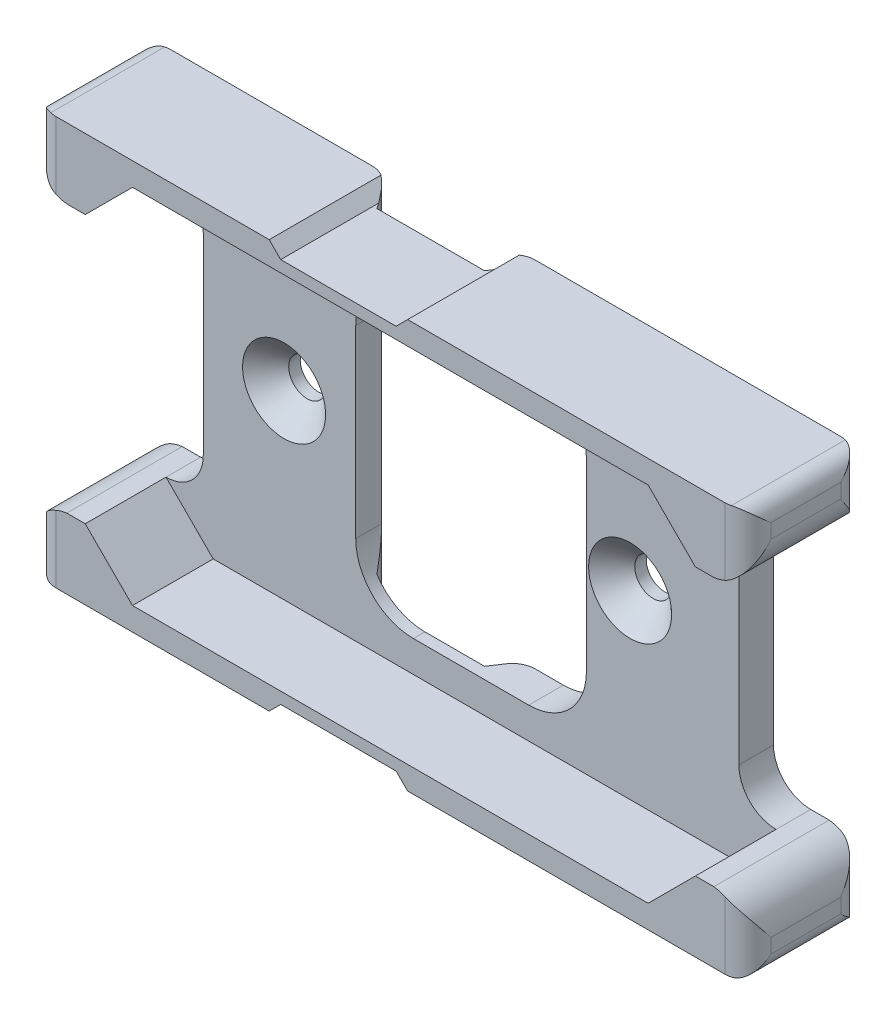
SolidWorks part; units mm, degrees
material "PET"
ref_plane "Front Plane" through (0, 0, 0) normal (0, 0, 1) x (1, 0, 0)
ref_plane "Top Plane" through (0, 0, 0) normal (0, 1, 0) x (1, 0, 0)
ref_plane "Right Plane" through (0, 0, 0) normal (1, 0, 0) x (0, 0, -1)
sketch "Sketch1" plane through (0, 0, 0) normal (0, 0, 1) x (1, 0, 0)
  line L0 (-31, 0) -> (31, 0)
  line L1 (31, 0) -> (31, 2.75)
  line L2 (28.0482, 6.094) -> (26.4482, 6.094)
  line L3 (26.4482, 6.094) -> (22.3542, 2)
  line L4 (22.3542, 2) -> (-22.3542, 2)
  line L5 (0, -3.5946) -> (0, 25.5961) construction
  line L6 (31, 17.7) -> (-31.0965, 17.7) construction
  line L7 (-26.4482, 6.094) -> (-22.3542, 2)
  line L8 (-31, 0) -> (-31, 2.75)
  line L9 (-28.0482, 6.094) -> (-26.4482, 6.094)
  line L10 (-28.0482, 29.306) -> (-26.4482, 29.306)
  line L11 (-31, 35.4) -> (-31, 32.65)
  line L12 (-26.4482, 29.306) -> (-22.3542, 33.4)
  line L13 (22.3542, 33.4) -> (-22.3542, 33.4)
  line L14 (26.4482, 29.306) -> (22.3542, 33.4)
  line L15 (28.0482, 29.306) -> (26.4482, 29.306)
  line L16 (31, 35.4) -> (31, 32.65)
  line L17 (-31, 35.4) -> (31, 35.4)
  arc A0 (31, 2.75) -> (28.0482, 6.094) centre (27.63, 2.75) ccw
  arc A1 (-31, 2.75) -> (-28.0482, 6.094) centre (-27.63, 2.75) cw
  arc A2 (-31, 32.65) -> (-28.0482, 29.306) centre (-27.63, 32.65) ccw
  arc A3 (31, 32.65) -> (28.0482, 29.306) centre (27.63, 32.65) cw
  point P18 (0, 2)
  point P19 (0, 0)
  point P25 (0, 35.4)
  point P26 (0, 33.4)
  dimension "D1" = 31
  dimension "D5" = 3.37
  dimension "D2" = 0.75
  dimension "D3" = 1.6
  dimension "D4" = 135
  dimension "D6" = 2
  dimension "D7" = 17.7
extrude "PCB Edge Guide" add sketch "Sketch1" along normal blind 7
sketch "Sketch2" plane through (0, 0, 0) normal (0, 0, -1) x (-1, 0, 0)
  line L1 (-31, 35.4) -> (31, 35.4)
  line L2 (-31, 35.4) -> (-31, 0)
  line L3 (-31, 0) -> (31, 0)
  line L4 (31, 35.4) -> (31, 0)
extrude "Rear Main Body" add sketch "Sketch2" along normal blind 3
fillet "Fillet1" radius 1.5 4 edges at (31, 0, 2) (31, 35.4, 2) (-31, 0, 2) (-31, 35.4, 2)
sketch "Sketch3" plane through (0, 2, 0) normal (0, 1, 0) x (1, 0, 0)
  line L0 (22.3542, -7) -> (-22.3542, -7) construction
  line L1 (-14, -7) -> (6, -7)
  line L2 (-14, -7) -> (-14, -4.7)
  line L3 (-14, -4.7) -> (6, -4.7)
  line L4 (6, -7) -> (6, -4.7)
  line L5 (0, 0) -> (0, -7) construction
  line L6 (22.3542, 0) -> (-22.3542, 0) construction
  dimension "D1" = 2.3
  dimension "D2" = 20
  dimension "D3" = 6
extrude "Lower PCB Fixture Tab" [suppressed] add sketch "Sketch3" along normal blind 2
sketch "Sketch4" plane through (0, 0, 7) normal (0, 0, 1) x (1, 0, 0)
  line L0 (0, 35.4) -> (0, 0) construction
  line L1 (29.5, 35.4) -> (-29.5, 35.4) construction
  line L2 (-31, 17.7) -> (31, 17.7) construction
  line L3 (-31, 2.75) -> (-31, 32.65) construction
  line L4 (31, 32.65) -> (31, 2.75) construction
  line L5 (-9, 0) -> (-9, 1)
  line L6 (0, 35.4) -> (-9, 35.4)
  line L7 (0, 35.4) -> (0, 34.4)
  line L8 (0, 34.4) -> (-9, 34.4)
  line L9 (-9, 35.4) -> (-9, 34.4)
  line L10 (0, 1) -> (-9, 1)
  line L11 (0, 0) -> (0, 1)
  line L12 (0, 0) -> (-9, 0)
  dimension "D1" = 1
  dimension "D2" = 9
extrude "Cable Tie Cutout" cut sketch "Sketch4" against normal through all
chamfer "Cable Tie Chamfer1" distance 1.5 angle 45 4 edges at (-9, 0, 2) (0, 0, 2) (-9, 35.4, 2) (0, 35.4, 2)
chamfer "Cable Tie Chamfer2" distance 1.5 angle 45 2 edges at (-4.5, 34.4, -3) (-4.5, 1, -3)
sketch "Sketch5" plane through (0, 0, -3) normal (0, 0, -1) x (-1, 0, 0)
  line L0 (-31, 17.7) -> (31, 17.7) construction
  line L1 (8, 30.7) -> (10, 30.7)
  line L2 (8, 30.7) -> (8, 4.7)
  line L3 (8, 4.7) -> (10, 4.7)
  line L4 (10, 30.7) -> (10, 4.7)
  line L5 (-31, 33.9) -> (-31, 1.5) construction
  line L6 (31, 1.5) -> (31, 33.9) construction
  line L7 (3.5, 30.7) -> (5.5, 30.7)
  line L8 (5.5, 30.7) -> (5.5, 4.7)
  line L9 (3.5, 30.7) -> (3.5, 4.7)
  line L10 (3.5, 4.7) -> (5.5, 4.7)
  line L11 (-1, 30.7) -> (1, 30.7)
  line L12 (1, 30.7) -> (1, 4.7)
  line L13 (-1, 30.7) -> (-1, 4.7)
  line L14 (-1, 4.7) -> (1, 4.7)
  line L15 (-5.5, 30.7) -> (-3.5, 30.7)
  line L16 (-3.5, 30.7) -> (-3.5, 4.7)
  line L17 (-5.5, 30.7) -> (-5.5, 4.7)
  line L18 (-5.5, 4.7) -> (-3.5, 4.7)
  line L19 (-10, 30.7) -> (-8, 30.7)
  line L20 (-8, 30.7) -> (-8, 4.7)
  line L21 (-10, 30.7) -> (-10, 4.7)
  line L22 (-10, 4.7) -> (-8, 4.7)
  dimension "D1" = 26
  dimension "D2" = 2
  dimension "D3" = 21
  dimension "D4" = 5
extrude "Rear Vents" cut sketch "Sketch5" against normal up to surface (3 mm away) up to face at (0, 17.7, 0)
sketch "Sketch6" plane through (0, 0, -3) normal (0, 0, -1) x (-1, 0, 0)
  line L0 (-31, 17.7) -> (31, 17.7) construction
  line L1 (-31, 33.9) -> (-31, 1.5) construction
  line L2 (31, 1.5) -> (31, 33.9) construction
  circle A0 centre (-13.79, 17.7) radius 1.6
  circle A1 centre (16.21, 17.7) radius 1.6
  dimension "D1" = 30
  dimension "D3" = 3.2
  dimension "D2" = 17.21
extrude "Cut-Extrude3" cut sketch "Sketch6" against normal up to next
chamfer "Chamfer3" distance 2 angle 45 2 edges at (-17.81, 17.7, 0) (12.19, 17.7, 0)
sketch "Sketch7" plane through (0, 0, -3) normal (0, 0, -1) x (-1, 0, 0)
  line L0 (31, 17.7) -> (-31, 17.7) construction
  line L1 (31, 1.5) -> (31, 33.9) construction
  line L2 (-31, 33.9) -> (-31, 1.5) construction
  line L3 (-8, 30.7) -> (-10, 30.7) construction
  line L4 (21.46, 4.7) -> (10.96, 4.7)
  line L5 (21.46, 4.7) -> (21.46, 30.7)
  line L6 (21.46, 30.7) -> (10.96, 30.7)
  line L7 (10.96, 4.7) -> (10.96, 30.7)
  line L8 (-8.54, 4.7) -> (-19.04, 4.7)
  line L9 (-8.54, 4.7) -> (-8.54, 30.7)
  line L10 (-8.54, 30.7) -> (-19.04, 30.7)
  line L11 (-19.04, 4.7) -> (-19.04, 30.7)
  line L12 (-10, 4.7) -> (-8, 4.7) construction
  line L13 (16.21, 35.4) -> (16.21, 0) construction
  line L14 (-13.79, 35.4) -> (-13.79, 0) construction
  line L15 (-29.5, 0) -> (-1.5, 0) construction
  point P22 (16.21, 17.7)
  point P28 (-13.79, 17.7)
  dimension "D1" = 10.5
  dimension "D2" = 10.5
extrude "Cut-Extrude4" [suppressed] cut sketch "Sketch7" against normal blind 1
sketch "Sketch8" plane through (0, 0, -3) normal (0, 0, -1) x (-1, 0, 0)
  line L0 (26.4482, 6.094) -> (28.0482, 6.094) construction
  line L1 (-28.0482, 6.094) -> (-26.4482, 6.094) construction
  line L2 (-26.4482, 29.306) -> (-28.0482, 29.306) construction
  line L3 (28.0482, 29.306) -> (26.4482, 29.306) construction
  line L4 (-28.0482, 6.094) -> (-26.4482, 6.094)
  line L5 (-26.4482, 29.306) -> (-28.0482, 29.306)
  line L6 (28.0482, 29.306) -> (26.4482, 29.306)
  line L7 (26.4482, 6.094) -> (28.0482, 6.094)
  line L8 (31, 2.75) -> (31.4444, 2.75)
  line L9 (31.4444, 2.75) -> (31.4444, 32.65)
  line L10 (31.4444, 32.65) -> (31, 32.65)
  line L11 (-31, 2.75) -> (-31.9815, 2.75)
  line L12 (-31.9815, 2.75) -> (-31.9815, 32.65)
  line L13 (-31.9815, 32.65) -> (-31, 32.65)
  line L14 (-31, 1.5) -> (31, 1.5) construction
  line L15 (0, -35.3244) -> (0, 38.3457) construction
  line L16 (31, 17.7) -> (-31, 17.7) construction
  line L17 (31, 1.5) -> (31, 33.9) construction
  line L18 (-31, 33.9) -> (-31, 1.5) construction
  line L19 (23.2182, 9.324) -> (23.2182, 26.076)
  line L20 (-23.2182, 9.324) -> (-23.2182, 26.076)
  arc A0 (31, 2.75) -> (28.0482, 6.094) centre (27.63, 2.75) ccw construction
  arc A1 (-28.0482, 6.094) -> (-31, 2.75) centre (-27.63, 2.75) ccw construction
  arc A2 (-31, 32.65) -> (-28.0482, 29.306) centre (-27.63, 32.65) ccw construction
  arc A3 (28.0482, 29.306) -> (31, 32.65) centre (27.63, 32.65) ccw construction
  arc A4 (-28.0482, 6.094) -> (-31, 2.75) centre (-27.63, 2.75) ccw
  arc A5 (-31, 32.65) -> (-28.0482, 29.306) centre (-27.63, 32.65) ccw
  arc A6 (28.0482, 29.306) -> (31, 32.65) centre (27.63, 32.65) ccw
  arc A7 (31, 2.75) -> (28.0482, 6.094) centre (27.63, 2.75) ccw
  arc A8 (26.4482, 6.094) -> (23.2182, 9.324) centre (26.4482, 9.324) cw
  arc A11 (26.4482, 29.306) -> (23.2182, 26.076) centre (26.4482, 26.076) ccw
  arc A12 (-26.4482, 29.306) -> (-23.2182, 26.076) centre (-26.4482, 26.076) cw
  arc A13 (-26.4482, 6.094) -> (-23.2182, 9.324) centre (-26.4482, 9.324) ccw
  point P27 (-31, 1.5)
  point P29 (0, 1.5107)
  point P30 (0, 1.5)
  point P43 (23.2182, 17.7)
  dimension "D1" = 3.23
extrude "Cut-Extrude5" cut sketch "Sketch8" against normal up to next
sketch "Sketch9" plane through (0, 0, 0) normal (0, -1, 0) x (-1, 0, 0)
  line L0 (10.5, 3) -> (9.1667, 1)
  line L1 (9.1667, 1) -> (-0.1667, 1)
  line L2 (-0.1667, 1) -> (-1.5, 3)
  line L3 (-1.5, 3) -> (10.5, 3)
  dimension "D1" = 56.31
  dimension "D2" = 56.31
  dimension "D3" = 2
extrude "Cut-Extrude6" cut sketch "Sketch9" against normal through all
sketch "Sketch10" plane through (0, 0, 0) normal (0, -1, 0) x (-1, 0, 0)
  line L0 (31, -7) -> (31, -5)
  line L1 (31, 3) -> (31, -7) construction
  line L2 (31, -7) -> (29, -7)
  line L3 (29.5, -7) -> (10.5, -7) construction
  line L4 (-29.5, -2) -> (29.5, -2) construction
  line L5 (-29.5, 3) -> (-29.5, -7) construction
  line L6 (29.5, -7) -> (29.5, 3) construction
  line L7 (0, -2) -> (0, -8.4106) construction
  line L8 (-31, -7) -> (-29, -7)
  line L9 (-31, -7) -> (-31, -5)
  line L10 (31, -7) -> (31, 3) construction
  line L13 (29.5, 3) -> (10.5, 3) construction
  line L14 (31, 1.0635) -> (31, 3)
  line L15 (31, 3) -> (29.5, 3) construction
  line L16 (31, 3) -> (29.0013, 3)
  line L17 (-31, 1.0635) -> (-31, 3)
  line L18 (-31, 3) -> (-29.0013, 3)
  arc A0 (29, -7) -> (31, -5) centre (29, -5) ccw
  arc A1 (-29, -7) -> (-31, -5) centre (-29, -5) cw
  arc A2 (31, 1.0635) -> (29.0013, 3) centre (29.001, 1) ccw
  arc A3 (-31, 1.0635) -> (-29.0013, 3) centre (-29.001, 1) cw
  dimension "D1" = 2
  dimension "D3" = 2
  dimension "D2" = 2
extrude "Cut-Extrude7" cut sketch "Sketch10" against normal through all
fillet "Fillet2" radius 2 2 edges at (-10.5, 17.7, -3) (1.5, 17.7, -3)
sketch "Sketch12" [suppressed] plane through (0, 0, -2) normal (0, 0, -1) x (-1, 0, 0)
  line L2 (-19.04, 30.7) -> (-19.04, 4.7) construction
  line L5 (21.46, 4.7) -> (21.46, 30.7) construction
  line L6 (-9.04, 4.7) -> (-9.04, 30.7)
  line L7 (-19.04, 4.7) -> (-9.04, 4.7)
  line L8 (-19.04, 30.7) -> (-19.04, 4.7)
  line L9 (11.46, 30.7) -> (11.46, 4.7)
  line L10 (11.46, 4.7) -> (21.46, 4.7)
  line L11 (21.46, 4.7) -> (21.46, 30.7)
  line L12 (-19.04, 30.7) -> (-9.04, 30.7)
  line L13 (11.46, 30.7) -> (21.46, 30.7)
  dimension "D1" = 10
  dimension "D2" = 10
extrude "Boss-Extrude1" [suppressed] add sketch "Sketch12" along normal blind 19
fillet "Fillet3" [suppressed] radius 5
sketch "Sketch11" plane through (0, 0, 0) normal (0, 0, 1) x (1, 0, 0)
  line L0 (-33.6648, 17.7) -> (34.6704, 17.7) construction
  line L2 (-32.3574, 17.7) -> (33.1116, 17.7)
  line L3 (-32.3574, 17.7) -> (-32.3574, 35.978)
  line L4 (-32.3574, 35.978) -> (33.1116, 35.978)
  line L5 (33.1116, 17.7) -> (33.1116, 35.978)
extrude "Cut-Extrude8" [suppressed] cut sketch "Sketch11" against normal up to next
sketch "Sketch14" [suppressed] plane through (0, 17.7, 0) normal (0, 1, 0) x (1, 0, 0)
  line L0 (8, 0) -> (8, 3) construction
  line L1 (8, 3) -> (5.5, 3) construction
  line L2 (5.5, 3) -> (5.5, 0) construction
  line L3 (5.5, 0) -> (8, 0) construction
  line L4 (3.5, 0) -> (3.5, 3) construction
  line L5 (3.5, 3) -> (2.5704, 3) construction
  line L6 (1, 2.2385) -> (1, 0) construction
  line L7 (1, 0) -> (3.5, 0) construction
  line L8 (-1, 0) -> (-1, 1) construction
  line L9 (-1, 1) -> (-3.5, 1) construction
  line L10 (-3.5, 1) -> (-3.5, 0) construction
  line L11 (-3.5, 0) -> (-1, 0) construction
  line L12 (-5.5, 0) -> (-5.5, 1) construction
  line L13 (-5.5, 1) -> (-8, 1) construction
  line L14 (-8, 1) -> (-8, 0) construction
  line L15 (-8, 0) -> (-5.5, 0) construction
  line L16 (8, 0) -> (8, 3)
  line L17 (8, 3) -> (5.5, 3)
  line L18 (5.5, 3) -> (5.5, 0)
  line L19 (5.5, 0) -> (8, 0)
  line L20 (3.5, 0) -> (3.5, 3)
  line L21 (3.5, 3) -> (2.5704, 3)
  line L22 (1, 2.2385) -> (1, 0)
  line L23 (1, 0) -> (3.5, 0)
  line L24 (-1, 0) -> (-1, 1)
  line L25 (-1, 1) -> (-3.5, 1)
  line L26 (-3.5, 1) -> (-3.5, 0)
  line L27 (-3.5, 0) -> (-1, 0)
  line L28 (-5.5, 0) -> (-5.5, 1)
  line L29 (-5.5, 1) -> (-8, 1)
  line L30 (-8, 1) -> (-8, 0)
  line L31 (-8, 0) -> (-5.5, 0)
  line L32 (-11.46, 2) -> (-11.46, 0)
  line L33 (-12.61, 0) -> (-10, 0) construction
  line L34 (-11.46, 0) -> (-10, 0)
  line L35 (-10, 0) -> (-10, 2.2385)
  line L36 (-10.96, 2.9046) -> (-10.96, 2)
  line L37 (-10.96, 2) -> (-11.46, 2)
  arc A0 (2.5704, 3) -> (1, 2.2385) centre (2.5704, 1) ccw construction
  arc A1 (2.5704, 3) -> (1, 2.2385) centre (2.5704, 1) ccw
  arc A3 (-10, 2.2385) -> (-10.96, 2.9046) centre (-11.5704, 1) ccw construction
  arc A4 (-10, 2.2385) -> (-10.96, 2.9046) centre (-11.5704, 1) ccw
extrude "Cut-Extrude10" [suppressed] cut sketch "Sketch14" against normal up to surface (13 mm away)
sketch "Sketch13" [suppressed] plane through (0, 17.7, 0) normal (0, 1, 0) x (1, 0, 0)
  circle A0 centre (14.04, 12) radius 1.6
  circle A1 centre (-16.46, 12) radius 1.6
  dimension "D1" = 3.2
extrude "Cut-Extrude9" [suppressed] cut sketch "Sketch13" against normal up to next
sketch "Sketch15" [suppressed] plane through (0, 4.7, 0) normal (0, 1, 0) x (1, 0, 0)
  line L0 (9.04, 2) -> (9.04, 0)
  line L1 (-11.46, 0) -> (10, 0) construction
  line L2 (9.04, 0) -> (10, 0)
  line L3 (10, 0) -> (10, 2)
  line L4 (10, 2) -> (9.04, 2)
extrude "Boss-Extrude2" [suppressed] add sketch "Sketch15" along normal up to surface (13 mm away)
fillet "Fillet4" [suppressed] radius 5
sketch "Sketch16" [suppressed] plane through (0, 0, 7) normal (0, 0, 1) x (1, 0, 0)
  line L0 (-41.4661, 17.7) -> (44.662, 17.7) construction
  line L2 (-35.0211, 17.7) -> (33.0504, 17.7)
  line L3 (-35.0211, 17.7) -> (-35.0211, 0)
  line L4 (-35.0211, 0) -> (33.0504, 0)
  line L5 (33.0504, 17.7) -> (33.0504, 0)
extrude "Cut-Extrude11" [suppressed] cut sketch "Sketch16" against normal through all
sketch "Sketch17" [suppressed] plane through (0, 30.7, 0) normal (0, -1, 0) x (1, 0, 0)
  line L0 (8, 0) -> (5.5, 0) construction
  line L1 (5.5, 0) -> (5.5, -3) construction
  line L2 (5.5, -3) -> (8, -3) construction
  line L3 (8, -3) -> (8, 0) construction
  line L4 (3.5, 0) -> (1, 0) construction
  line L5 (1, 0) -> (1, -2.2385) construction
  line L6 (2.5704, -3) -> (3.5, -3) construction
  line L7 (3.5, -3) -> (3.5, 0) construction
  line L8 (-3.5, 0) -> (-3.5, -1) construction
  line L9 (-3.5, -1) -> (-1, -1) construction
  line L10 (-1, -1) -> (-1, 0) construction
  line L11 (-1, 0) -> (-3.5, 0) construction
  line L12 (-8, 0) -> (-8, -1) construction
  line L13 (-8, -1) -> (-5.5, -1) construction
  line L14 (-5.5, -1) -> (-5.5, 0) construction
  line L15 (-5.5, 0) -> (-8, 0) construction
  line L16 (8, 0) -> (5.5, 0)
  line L17 (5.5, 0) -> (5.5, -3)
  line L18 (5.5, -3) -> (8, -3)
  line L19 (8, -3) -> (8, 0)
  line L20 (3.5, 0) -> (1, 0)
  line L21 (1, 0) -> (1, -2.2385)
  line L22 (2.5704, -3) -> (3.5, -3)
  line L23 (3.5, -3) -> (3.5, 0)
  line L24 (-3.5, 0) -> (-3.5, -1)
  line L25 (-3.5, -1) -> (-1, -1)
  line L26 (-1, -1) -> (-1, 0)
  line L27 (-1, 0) -> (-3.5, 0)
  line L28 (-8, 0) -> (-8, -1)
  line L29 (-8, -1) -> (-5.5, -1)
  line L30 (-5.5, -1) -> (-5.5, 0)
  line L31 (-5.5, 0) -> (-8, 0)
  line L32 (-11.46, -2) -> (-11.46, 0)
  line L33 (-22.3542, 0) -> (22.3542, 0) construction
  line L34 (-11.46, 0) -> (-10, 0)
  line L35 (-10, 0) -> (-10, -2.2385)
  line L36 (-10, -2.2385) -> (-10, -3.1746)
  line L37 (-10, -3.1746) -> (-11.46, -3.1746)
  line L38 (-11.46, -2) -> (-11.46, -16) construction
  line L39 (-11.46, -3.1746) -> (-11.46, -2)
  arc A0 (1, -2.2385) -> (2.5704, -3) centre (2.5704, -1) ccw construction
  arc A1 (1, -2.2385) -> (2.5704, -3) centre (2.5704, -1) ccw
extrude "Cut-Extrude12" [suppressed] cut sketch "Sketch17" along normal up to surface (13 mm away)
sketch "Sketch18" [suppressed] plane through (0, 30.7, 0) normal (0, -1, 0) x (1, 0, 0)
  line L0 (9.04, -2) -> (9.04, 0)
  line L1 (10, 0) -> (-11.46, 0) construction
  line L2 (9.04, 0) -> (10, 0)
  line L3 (-22.3542, 0) -> (22.3542, 0) construction
  line L4 (10, 0) -> (10, -2)
  line L5 (10, -2) -> (9.04, -2)
extrude "Boss-Extrude3" [suppressed] add sketch "Sketch18" along normal up to surface (13 mm away)
sketch "Sketch20" [suppressed] plane through (0, 30.7, 0) normal (0, 1, 0) x (1, 0, 0)
  circle A0 centre (14.04, 16) radius 1.6
  circle A1 centre (-16.46, 16) radius 1.6
  dimension "D1" = 3.2
extrude "Cut-Extrude13" [suppressed] cut sketch "Sketch20" against normal through all
fillet "Fillet5" [suppressed] radius 5
sketch "Sketch21" [suppressed] plane through (0, 0, 0) normal (0, 0, 1) x (1, 0, 0)
  line L1 (-19.81, 17.7) -> (-12.2241, 17.7)
  line L2 (-19.81, 17.7) -> (-19.81, 22.8215)
  line L3 (-19.81, 22.8215) -> (-12.2241, 22.8215)
  line L4 (-12.2241, 17.7) -> (-12.2241, 22.8215)
  line L5 (10.19, 17.7) -> (17.3907, 17.7)
  line L6 (10.19, 17.7) -> (10.19, 22.8215)
  line L7 (10.19, 22.8215) -> (17.3907, 22.8215)
  line L8 (17.3907, 17.7) -> (17.3907, 22.8215)
extrude "Boss-Extrude4" [suppressed] add sketch "Sketch21" against normal up to surface (2 mm away)
sketch "Sketch22" [suppressed] plane through (0, 0, 0) normal (0, 0, 1) x (1, 0, 0)
  line L1 (17.39, 17.7) -> (9.774, 17.7)
  line L2 (17.39, 17.7) -> (17.39, 12.3654)
  line L3 (17.39, 12.3654) -> (9.774, 12.3654)
  line L4 (9.774, 17.7) -> (9.774, 12.3654)
  line L5 (-12.61, 17.7) -> (-20.48, 17.7)
  line L6 (-12.61, 17.7) -> (-12.61, 12.3654)
  line L7 (-12.61, 12.3654) -> (-20.48, 12.3654)
  line L8 (-20.48, 17.7) -> (-20.48, 12.3654)
extrude "Boss-Extrude5" [suppressed] add sketch "Sketch22" against normal up to surface (2 mm away)
sketch "Sketch23" [suppressed] plane through (0, 33.4, 0) normal (0, -1, 0) x (1, 0, 0)
  line L0 (-22.3542, 7) -> (22.3542, 7) construction
  line L1 (-14, 7) -> (6, 7)
  line L2 (-14, 7) -> (-14, 4.7)
  line L3 (-14, 4.7) -> (6, 4.7)
  line L4 (6, 7) -> (6, 4.7)
  line L5 (-31, 5) -> (-31, -1.0635) construction
  dimension "D1" = 2.3
  dimension "D2" = 20
  dimension "D3" = 17
extrude "Boss-Extrude6" [suppressed] add sketch "Sketch23" along normal blind 2
chamfer "Chamfer4" [suppressed] distance 2 angle 45
chamfer "Chamfer5" [suppressed] distance 2 angle 45
sketch "Sketch24" plane through (0, 0, -3) normal (0, 0, -1) x (-1, 0, 0)
  line L1 (-10, 30.7) -> (10, 30.7)
  line L2 (-10, 30.7) -> (-10, 4.7)
  line L3 (-10, 4.7) -> (10, 4.7)
  line L4 (10, 30.7) -> (10, 4.7)
extrude "Cut-Extrude14" cut sketch "Sketch24" against normal through all
fillet "Fillet6" radius 5 4 edges at (-10, 30.7, -1.1193) (-10, 4.7, -1.1193) (10, 4.7, -1.5) (10, 30.7, -1.5)
